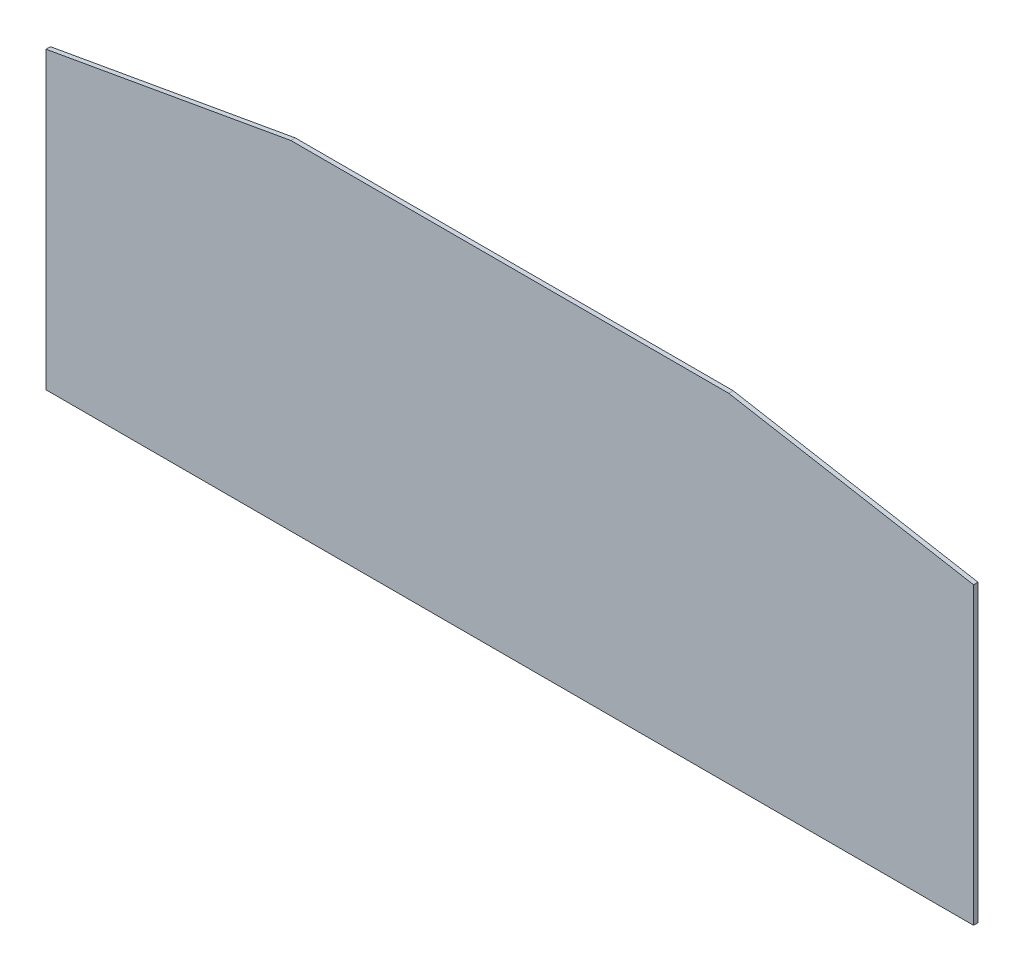
SolidWorks part; units mm, degrees
ref_plane "Ön Düzlem" through (0, 0, 0) normal (0, 0, 1) x (1, 0, 0)
ref_plane "Üst Düzlem" through (0, 0, 0) normal (0, 1, 0) x (1, 0, 0)
ref_plane "Sağ Düzlem" through (0, 0, 0) normal (1, 0, 0) x (0, 0, -1)
sketch "Çizim1" plane through (0, 0, 0) normal (0, 0, 1) x (1, 0, 0)
  line L0 (0, 0) -> (0, 795)
  line L1 (0, 795) -> (660, 912)
  line L2 (660, 912) -> (1840, 912)
  line L3 (1840, 912) -> (2500, 795)
  line L4 (2500, 795) -> (2500, 0)
  line L5 (2500, 0) -> (0, 0)
  line L6 (640, 908.4545) -> (640, 0) construction
  dimension "D1" = 795
  dimension "D2" = 912
  dimension "D3" = 660
  dimension "D4" = 660
  dimension "D5" = 2500
  dimension "D6" = 640
  dimension "D7" = 908.4545
  dimension "D8" = 113.4545
  dimension "D9" = 640
base flange "Taban-Flanş1" sketch "Çizim1" thickness 12 reverse thickness direction no parameters "D1"=8
sketch "Büküm-Çizgileri1" [suppressed] plane through (0, 0, 0) normal (0, 1, 0) x (1, 0, 0)
sketch "Sınırlandırma-Kutusu1" [suppressed] plane through (0, 0, 0) normal (0, 1, 0) x (1, 0, 0)
sheet metal parameters "Sac-Levha1" thickness 12 parameters "D1"=8
flat pattern "Düz-Çoğaltma1" [suppressed]
sketch "Büküm-Çizgileri2" plane through (0, 0, 0) normal (0, 1, 0) x (1, 0, 0)
sketch3d "Sınırlandırma-Kutusu2" [suppressed]
  line L0 (0, 0, 0) -> (2500, 0, 0) construction
  line L1 (0, 912, 0) -> (2500, 912, 0) construction
  line L2 (0, 0, 0) -> (0, 912, 0) construction
  line L3 (2500, 0, 0) -> (2500, 912, 0) construction
